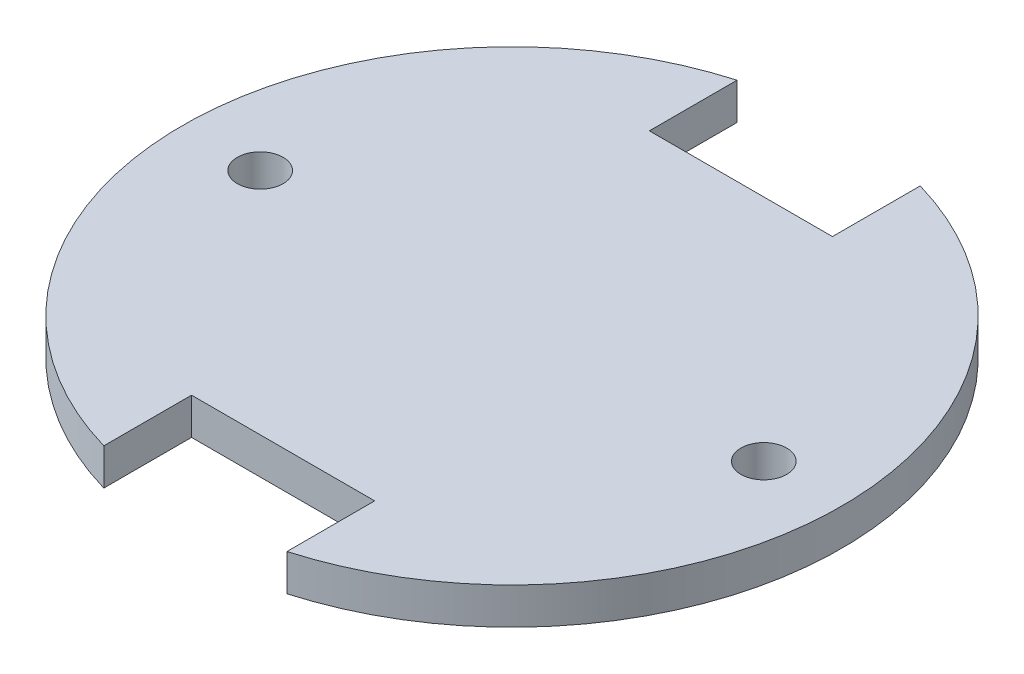
SolidWorks part; units mm, degrees
material "Balsa"
ref_plane "Front Plane" through (0, 0, 0) normal (0, 0, 1) x (1, 0, 0)
ref_plane "Top Plane" through (0, 0, 0) normal (0, 1, 0) x (1, 0, 0)
ref_plane "Right Plane" through (0, 0, 0) normal (1, 0, 0) x (0, 0, -1)
sketch "Sketch1" plane through (0, 0, 0) normal (0, 1, 0) x (1, 0, 0)
  line L0 (-36, 0) -> (36, 0) construction
  line L1 (0, 36) -> (0, -36) construction
  line L2 (-10, 34.5832) -> (-10, 25)
  line L3 (-10, 25) -> (10, 25)
  line L4 (10, 25) -> (10, 34.5832)
  line L5 (10, -25) -> (10, -34.5832)
  line L6 (-10, -25) -> (10, -25)
  line L7 (-10, -34.5832) -> (-10, -25)
  arc A0 (-10, 34.5832) -> (-10, -34.5832) centre (0, 0) ccw
  circle A1 centre (-27.5, 0) radius 2.5
  circle A2 centre (27.5, 0) radius 2.5
  arc A3 (10, -34.5832) -> (10, 34.5832) centre (0, 0) ccw
  point P1 (0, 0)
  dimension "D1" = 55
  dimension "D2" = 36
  dimension "D3" = 5
  dimension "D4" = 20
  dimension "D5" = 50
extrude "Boss-Extrude1" add sketch "Sketch1" along normal blind 4
